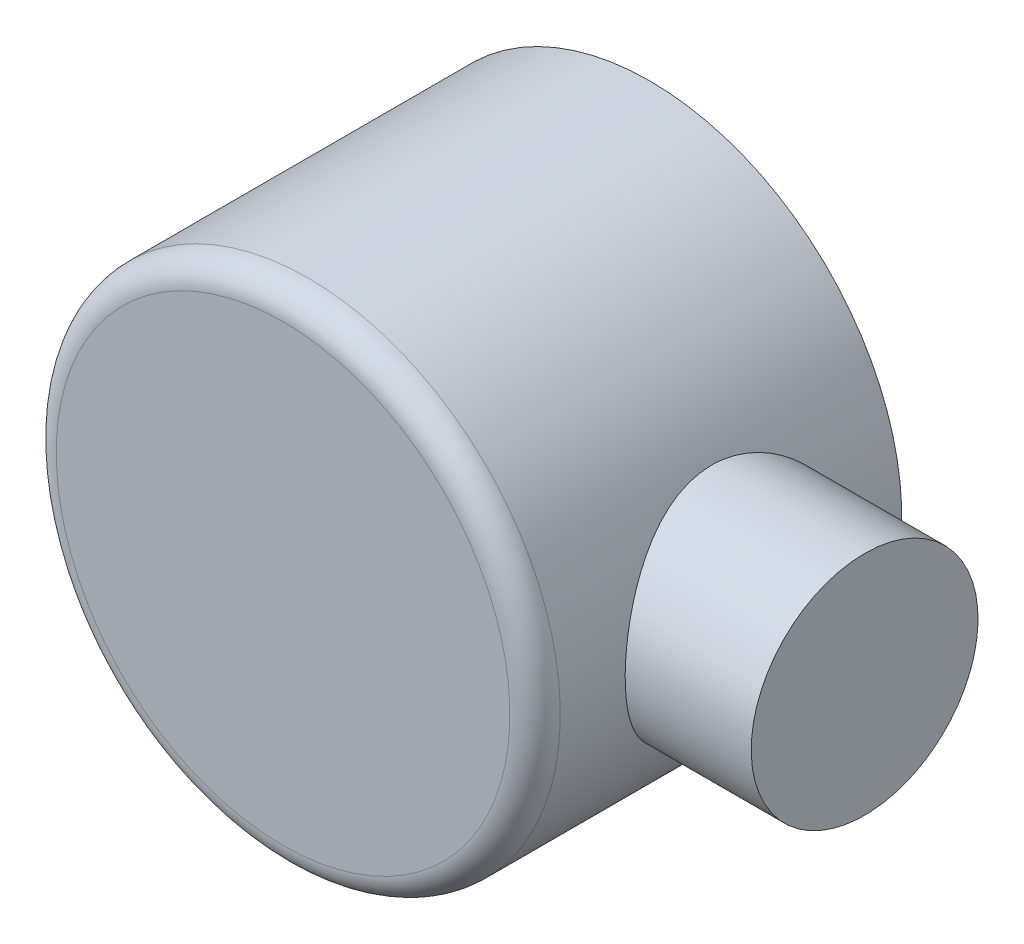
SolidWorks part; units mm, degrees
material "Cast Stainless Steel"
ref_plane "Front Plane" through (0, 0, 0) normal (0, 0, 1) x (1, 0, 0)
ref_plane "Top Plane" through (0, 0, 0) normal (0, 1, 0) x (1, 0, 0)
ref_plane "Right Plane" through (0, 0, 0) normal (1, 0, 0) x (0, 0, -1)
other "Center of Mass"
sketch "Sketch2" plane through (0, 0, 0) normal (1, 0, 0) x (0, 0, -1)
  circle A0 centre (0, 0) radius 50
  dimension "D1" = 100
extrude "Boss-Extrude1" add sketch "Sketch2" along normal blind 64.75
ref_plane "Plane1" through (32.375, 0, 0) normal (-1, 0, 0) x (0, 0, 1)
sketch "Sketch3" plane through (32.375, 0, 0) normal (-1, 0, 0) x (0, 0, 1)
  line L0 (0, 50) -> (0, 75)
  line L1 (0, 75) -> (22.5, 75)
  line L2 (0, 75) -> (-22.5, 75)
  line L3 (-22.5, 75) -> (-22.5, 44.6514)
  line L4 (22.5, 75) -> (22.5, 44.6514)
  circle A1 centre (0, 0) radius 50
  circle A2 centre (0, 0) radius 50
  dimension "D2" = 25
  dimension "D3" = 22.5
  dimension "D4" = 22.5
  dimension "D1" = 0
revolve "Revolve1" add sketch "Sketch3" angle 360 about L0 region at (32.375, 61.5818, 11.6206)
sketch "Sketch4" plane through (0, 0, 0) normal (-1, 0, 0) x (0, 0, 1)
  circle A1 centre (0, 0) radius 50
  circle A2 centre (0, 0) radius 50
  dimension "D1" = 0
extrude "Boss-Extrude2" add sketch "Sketch4" along normal blind 8
fillet "Fillet1" radius 5 1 edges at (-8, 0, 50)
ref_plane "Plane3" through (32.38, 0, 0) normal (-1, 0, 0) x (0, 0, 1)
ref_axis "Axis2" through (32.375, 75, 0) along (0, -1, 0)
ref_axis "Axis3" through (64.75, 0, 0) along (-1, 0, 0)
ref_point "Point1"
move or copy body "Body-Move/Copy1" bodies to move or copy 103 copy no translate (-32.38, 0, 0)
move or copy body "Body-Move/Copy2" bodies to move or copy 107 copy no rotation origin (0, 0, 0) rotation axis (0.5774, 0.5774, -0.5774) rotation angle 120
